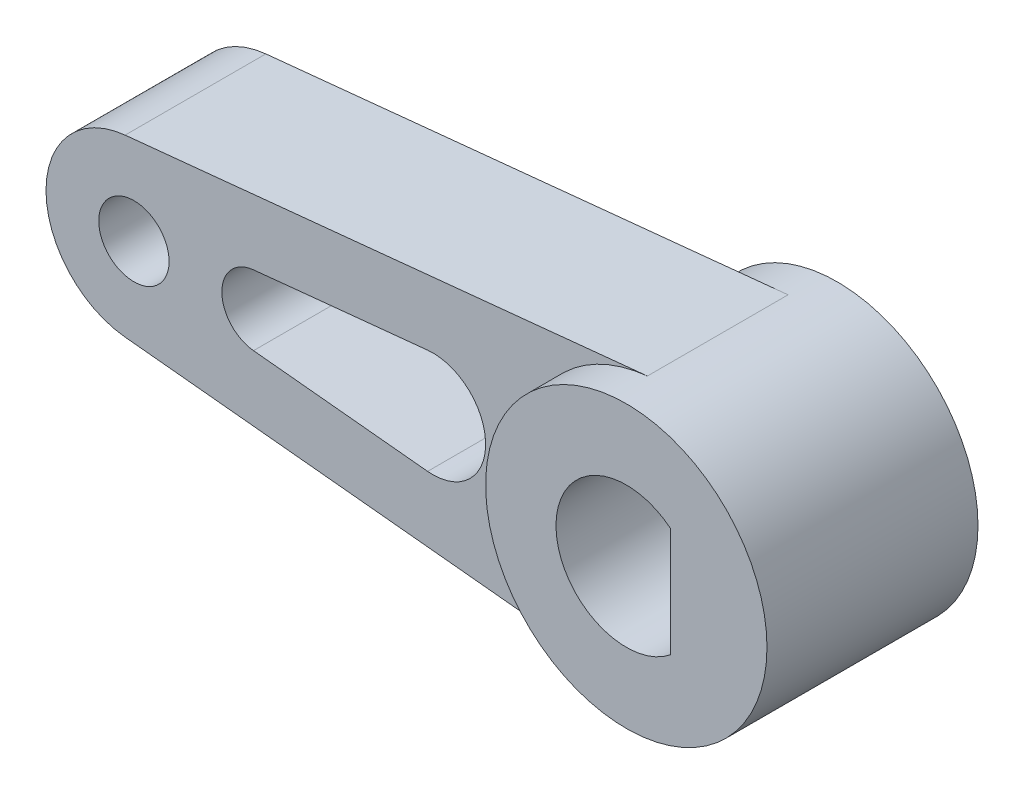
SolidWorks part; units mm, degrees
material "1060 合金"
ref_plane "前视基准面" through (0, 0, 0) normal (0, 0, 1) x (1, 0, 0)
ref_plane "上视基准面" through (0, 0, 0) normal (0, 1, 0) x (1, 0, 0)
ref_plane "右视基准面" through (0, 0, 0) normal (1, 0, 0) x (0, 0, -1)
sketch "草图1" plane through (0, 0, 0) normal (0, 0, 1) x (1, 0, 0)
  line L0 (-30.5, 4.9749) -> (-0.8, 7.9599)
  line L1 (-0.8, -7.9599) -> (-30.5, -4.9749)
  line L2 (-35, 0) -> (8, 0) construction
  line L5 (-23.2, 1.99) -> (-13.3, 2.985)
  line L6 (-13.3, -2.985) -> (-23.2, -1.99)
  line L7 (2.5, 3.1225) -> (2.5, -3.1225)
  arc A0 (2.5, 3.1225) -> (2.5, -3.1225) centre (0, 0) ccw
  circle A1 centre (-30, 0) radius 2
  arc A2 (-0.8, -7.9599) -> (-0.8, 7.9599) centre (0, 0) ccw
  arc A3 (-30.5, 4.9749) -> (-30.5, -4.9749) centre (-30, 0) ccw
  arc A6 (-23.2, 1.99) -> (-23.2, -1.99) centre (-23, 0) ccw
  arc A7 (-13.3, -2.985) -> (-13.3, 2.985) centre (-13, 0) ccw
  dimension "D1" = 4
  dimension "D2" = 8
  dimension "D3" = 8
  dimension "D4" = 5
  dimension "D6" = 3
  dimension "D7" = 2
  dimension "D5" = 30
  dimension "D8" = 13
  dimension "D9" = 7
  dimension "D10" = 2.5
extrude "凸台-拉伸1" add sketch "草图1" along normal mid plane 12
sketch "草图2" plane through (0, 0, 0) normal (0, 0, 1) x (1, 0, 0)
  line L0 (-30.5, -4.9749) -> (-0.8, -7.9599) construction
  line L1 (-0.8, 7.9599) -> (-30.5, 4.9749) construction
  line L2 (-30.5, -4.9749) -> (-0.8, -7.9599)
  line L3 (-0.8, 7.9599) -> (-30.5, 4.9749)
  arc A1 (-30.5, 4.9749) -> (-30.5, -4.9749) centre (-30, 0) ccw construction
  arc A3 (-30.5, 4.9749) -> (-30.5, -4.9749) centre (-30, 0) ccw
  arc A4 (-0.8, 7.9599) -> (-0.8, -7.9599) centre (0, 0) ccw
  arc A5 (-0.8, -7.9599) -> (-0.8, 7.9599) centre (0, 0) ccw construction
extrude "切除-拉伸2" cut sketch "草图2" along normal blind 2 from surface starting at face at (-0.75, 0, -6)
extrude "切除-拉伸3" cut sketch "草图2<2>" against normal blind 2 from surface starting at face at (-14.575, 0, 6)
sketch "草图2<2>" plane through (0, 0, 0) normal (0, 0, 1) x (1, 0, 0) same geometry as "草图2"
